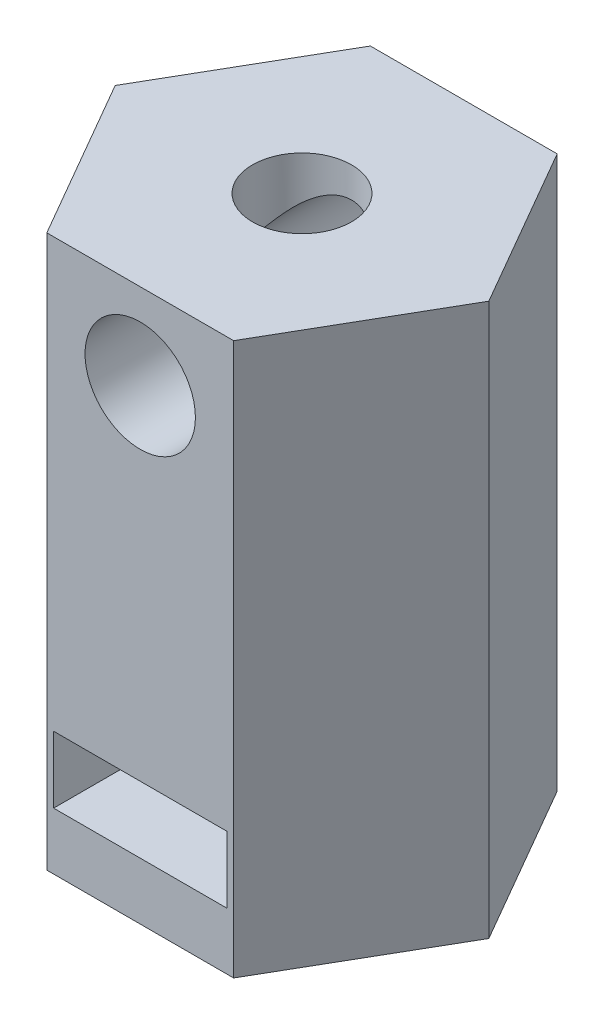
SolidWorks part; units mm, degrees
ref_plane "Front Plane" through (0, 0, 0) normal (0, 0, 1) x (1, 0, 0)
ref_plane "Top Plane" through (0, 0, 0) normal (0, 1, 0) x (1, 0, 0)
ref_plane "Right Plane" through (0, 0, 0) normal (1, 0, 0) x (0, 0, -1)
sketch "Sketch2" plane through (0, 0, 0) normal (0, 1, 0) x (1, 0, 0)
  line L1 (9.815, 0) -> (4.9075, 8.5)
  line L2 (4.9075, 8.5) -> (-4.9075, 8.5)
  line L3 (-4.9075, 8.5) -> (-9.815, 0)
  line L4 (-9.815, 0) -> (-4.9075, -8.5)
  line L5 (-4.9075, -8.5) -> (4.9075, -8.5)
  line L6 (4.9075, -8.5) -> (9.815, 0)
  circle A0 centre (0, 0) radius 8.5 construction
  circle A1 centre (0, 0) radius 2.6
  dimension "D2" = 5.2
  dimension "D1" = 17
extrude "core" add sketch "Sketch2" along normal blind 12
sketch "Sketch5" plane through (0, 0, 8.5) normal (0, 0, 1) x (1, 0, 0)
  line L0 (0, 0) -> (0, 3)
  line L1 (-4.9075, 0) -> (4.9075, 0) construction
  line L2 (4.55, 3) -> (-4.55, 3)
  line L3 (-4.55, 3) -> (4.55, 3)
  line L4 (-4.55, 3) -> (-4.55, 6.5)
  line L5 (4.55, 3) -> (4.55, 6.5)
  line L6 (-4.55, 6.5) -> (4.55, 6.5)
  point P7 (0, 3)
  dimension "D1" = 3
  dimension "D2" = 9.1
  dimension "D3" = 3.5
extrude "hex-nut" cut sketch "Sketch5" against normal blind 14.2 contours L6 L4 L2 L5 | L3 L4 L6 L5 region at (0, 4.75, 8.5)
sketch "Sketch4" plane through (0, 12, 0) normal (0, 1, 0) x (1, 0, 0)
  line L1 (9.815, 0) -> (4.9075, 8.5)
  line L2 (4.9075, 8.5) -> (-4.9075, 8.5)
  line L3 (-4.9075, 8.5) -> (-9.815, 0)
  line L4 (-9.815, 0) -> (-4.9075, -8.5)
  line L5 (-4.9075, -8.5) -> (4.9075, -8.5)
  line L6 (4.9075, -8.5) -> (9.815, 0)
  circle A0 centre (0, 0) radius 8.5 construction
  circle A1 centre (0, 0) radius 2.6
  dimension "D1" = 5.2
  dimension "D2" = 17
extrude "bolt-guard" add sketch "Sketch4" along normal blind 2 contours L1 L2 L3 L4 L5 L6
sketch "Sketch7" plane through (0, 14, 0) normal (0, 1, 0) x (1, 0, 0)
  line L1 (9.815, 0) -> (4.9075, 8.5)
  line L2 (4.9075, 8.5) -> (-4.9075, 8.5)
  line L3 (-4.9075, 8.5) -> (-9.815, 0)
  line L4 (-9.815, 0) -> (-4.9075, -8.5)
  line L5 (-4.9075, -8.5) -> (4.9075, -8.5)
  line L6 (4.9075, -8.5) -> (9.815, 0)
  circle A0 centre (0, 0) radius 2.6
  circle A1 centre (0, 0) radius 8.5 construction
  dimension "D1" = 5.2
extrude "d-shaft" add sketch "Sketch7" along normal blind 15
sketch "Sketch8" plane through (0, 0, 8.5) normal (0, 0, 1) x (1, 0, 0)
  line L0 (0, 29) -> (0, 24.5)
  line L1 (-4.9075, 29) -> (4.9075, 29) construction
  circle A0 centre (0, 24.5) radius 2.9
  dimension "D2" = 5.8
  dimension "D1" = 4.5
extrude "set-screw" cut sketch "Sketch8" against normal through all contours A0 region at (-1.9926, 22.5074, 8.5)
sketch "Sketch9" plane through (0, 6.5, 0) normal (0, -1, 0) x (1, 0, 0)
  line L1 (4.55, 0) -> (2.275, 3.9404)
  line L2 (2.275, 3.9404) -> (-2.275, 3.9404)
  line L3 (-2.275, 3.9404) -> (-4.55, 0)
  line L4 (-4.55, 0) -> (-2.275, -3.9404)
  line L5 (-2.275, -3.9404) -> (2.275, -3.9404)
  line L6 (2.275, -3.9404) -> (4.55, 0)
  line L7 (4.55, -5.7) -> (-4.55, -5.7)
  line L8 (4.55, -5.7) -> (4.55, 0)
  line L9 (4.55, 0) -> (-4.55, 0)
  line L10 (-4.55, -5.7) -> (-4.55, 0)
  circle A0 centre (0, 0) radius 3.9404 construction
  line M13 (-4.55, 8.5) -> (-4.55, -5.7)
  line M14 (-4.55, -5.7) -> (4.55, -5.7)
  line M15 (4.55, -5.7) -> (4.55, 8.5)
extrude "Boss-Extrude1" add sketch "Sketch9" along normal through all contours L6 L5 L4 M13 M14 M15 region at (0, 6.5, -4.033)
